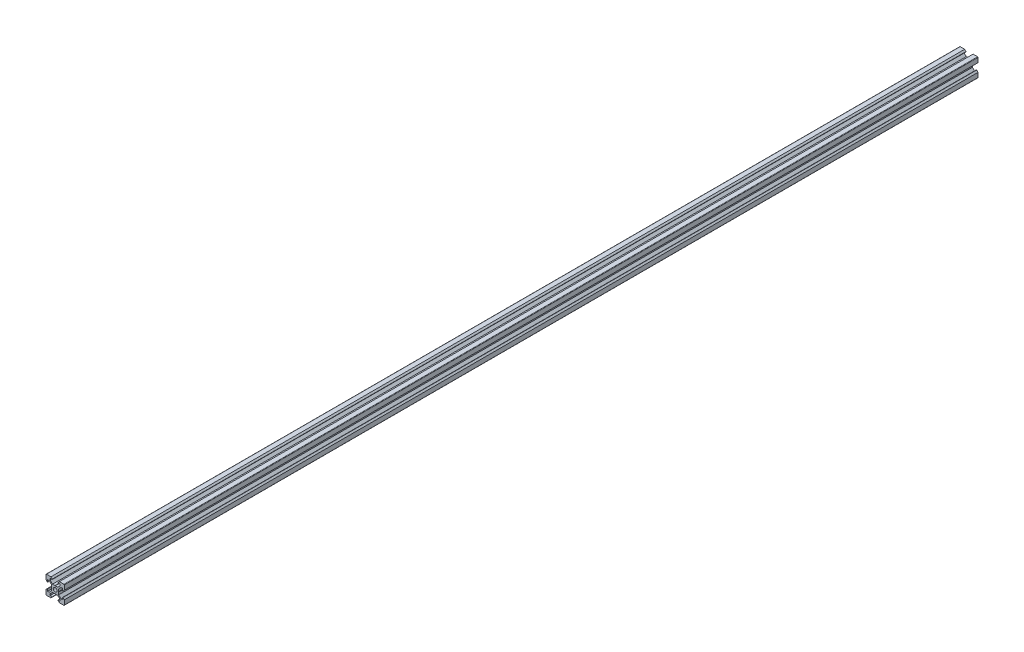
SolidWorks part; units mm, degrees
material "6061-T6 (SS)"
ref_plane "Front Plane" through (0, 0, 0) normal (0, 0, 1) x (1, 0, 0)
ref_plane "Top Plane" through (0, 0, 0) normal (0, 1, 0) x (1, 0, 0)
ref_plane "Right Plane" through (0, 0, 0) normal (1, 0, 0) x (0, 0, -1)
sketch "Sketch1" plane through (0, 0, 0) normal (0, 0, 1) x (1, 0, 0)
  line L1 (9.5, -10) -> (-9.5, -10)
  line L2 (10, -9.5) -> (10, 9.5)
  line L3 (9.5, 10) -> (-9.5, 10)
  line L4 (-10, -9.5) -> (-10, 9.5)
  line L5 (10, -10) -> (-10, 10) construction
  line L6 (10, 10) -> (-10, -10) construction
  circle A0 centre (0, 0) radius 2.1
  arc A1 (-9.5, 10) -> (-10, 9.5) centre (-9.5, 9.5) ccw
  arc A2 (10, 9.5) -> (9.5, 10) centre (9.5, 9.5) ccw
  arc A3 (9.5, -10) -> (10, -9.5) centre (9.5, -9.5) ccw
  arc A4 (-9.5, -10) -> (-10, -9.5) centre (-9.5, -9.5) cw
  point P0 (0, 0)
  line B0 (0, 0) -> (0, 10) construction
  line B1 (0, 3.69) -> (-0.21, 3.9)
  line B2 (-0.21, 3.9) -> (-2.8393, 3.9)
  line B3 (-2.8393, 3.9) -> (-5.5, 6.5607)
  line B4 (-5.5, 6.5607) -> (-5.5, 8.2)
  line B5 (-5.5, 8.2) -> (-3.125, 8.2)
  line B6 (-3.125, 8.2) -> (-3.125, 8.545)
  line B7 (-3.125, 8.545) -> (-4.58, 10)
  line B8 (-4.58, 10) -> (4.58, 10)
  line B9 (0, 0) -> (-5.9132, 5.9132) construction
  line B10 (3.125, 8.545) -> (4.58, 10)
  line B11 (3.125, 8.2) -> (3.125, 8.545)
  line B12 (5.5, 8.2) -> (3.125, 8.2)
  line B13 (5.5, 6.5607) -> (5.5, 8.2)
  line B14 (2.8393, 3.9) -> (5.5, 6.5607)
  line B15 (0.21, 3.9) -> (2.8393, 3.9)
  line B16 (0, 3.69) -> (0.21, 3.9)
  line B17 (0, 0) -> (-10, 0) construction
  line B18 (-3.69, 0) -> (-3.9, -0.21)
  line B19 (-3.9, -0.21) -> (-3.9, -2.8393)
  line B20 (-3.9, -2.8393) -> (-6.5607, -5.5)
  line B21 (-6.5607, -5.5) -> (-8.2, -5.5)
  line B22 (-8.2, -5.5) -> (-8.2, -3.125)
  line B23 (-8.2, -3.125) -> (-8.545, -3.125)
  line B24 (-8.545, -3.125) -> (-10, -4.58)
  line B25 (-10, -4.58) -> (-10, 4.58)
  line B26 (0, 0) -> (-5.9132, -5.9132) construction
  line B27 (-8.545, 3.125) -> (-10, 4.58)
  line B28 (-8.2, 3.125) -> (-8.545, 3.125)
  line B29 (-8.2, 5.5) -> (-8.2, 3.125)
  line B30 (-6.5607, 5.5) -> (-8.2, 5.5)
  line B31 (-3.9, 2.8393) -> (-6.5607, 5.5)
  line B32 (-3.9, 0.21) -> (-3.9, 2.8393)
  line B33 (-3.69, 0) -> (-3.9, 0.21)
  line B34 (0, 0) -> (0, -10) construction
  line B35 (0, -3.69) -> (0.21, -3.9)
  line B36 (0.21, -3.9) -> (2.8393, -3.9)
  line B37 (2.8393, -3.9) -> (5.5, -6.5607)
  line B38 (5.5, -6.5607) -> (5.5, -8.2)
  line B39 (5.5, -8.2) -> (3.125, -8.2)
  line B40 (3.125, -8.2) -> (3.125, -8.545)
  line B41 (3.125, -8.545) -> (4.58, -10)
  line B42 (4.58, -10) -> (-4.58, -10)
  line B43 (0, 0) -> (5.9132, -5.9132) construction
  line B44 (-3.125, -8.545) -> (-4.58, -10)
  line B45 (-3.125, -8.2) -> (-3.125, -8.545)
  line B46 (-5.5, -8.2) -> (-3.125, -8.2)
  line B47 (-5.5, -6.5607) -> (-5.5, -8.2)
  line B48 (-2.8393, -3.9) -> (-5.5, -6.5607)
  line B49 (-0.21, -3.9) -> (-2.8393, -3.9)
  line B50 (0, -3.69) -> (-0.21, -3.9)
  line B51 (0, 0) -> (10, 0) construction
  line B52 (3.69, 0) -> (3.9, 0.21)
  line B53 (3.9, 0.21) -> (3.9, 2.8393)
  line B54 (3.9, 2.8393) -> (6.5607, 5.5)
  line B55 (6.5607, 5.5) -> (8.2, 5.5)
  line B56 (8.2, 5.5) -> (8.2, 3.125)
  line B57 (8.2, 3.125) -> (8.545, 3.125)
  line B58 (8.545, 3.125) -> (10, 4.58)
  line B59 (10, 4.58) -> (10, -4.58)
  line B60 (0, 0) -> (5.9132, 5.9132) construction
  line B61 (8.545, -3.125) -> (10, -4.58)
  line B62 (8.2, -3.125) -> (8.545, -3.125)
  line B63 (8.2, -5.5) -> (8.2, -3.125)
  line B64 (6.5607, -5.5) -> (8.2, -5.5)
  line B65 (3.9, -2.8393) -> (6.5607, -5.5)
  line B66 (3.9, -0.21) -> (3.9, -2.8393)
  line B67 (3.69, 0) -> (3.9, -0.21)
  dimension "D1" = 4.2
  dimension "D3" = 0.5
  dimension "D2" = 20
sketch_block_instance "V Slot 1-4"
sketch_block "V Slot 1" parameters "D1"=10, "D2"=11, "D3"=4.3, "D4"=1.8, "D5"=0.21, "D6"=45, "D7"=9.16, "D8"=1.5, "D9"=6.25
sketch_block_instance "V Slot 1-5"
sketch_block_instance "V Slot 1-6"
sketch_block_instance "V Slot 1-7"
extrude "Boss-Extrude1" add sketch "Sketch1" along normal blind 1000 contours B67 B52 B53 B54 B55 B56 B57 B58 L2 A2 L3 B10 B11 B12 B13 B14 B15 B16 B1 B2 B3 B4 B5 B6 B7 A1 L4 B27 B28 B29 B30 B31 B32 B33 B18 B19 B20 B21 B22 B23 B24 A4 L1 B44 B45 B46 B47 B48 B49 region at (7.04, -9.7172, 0)
